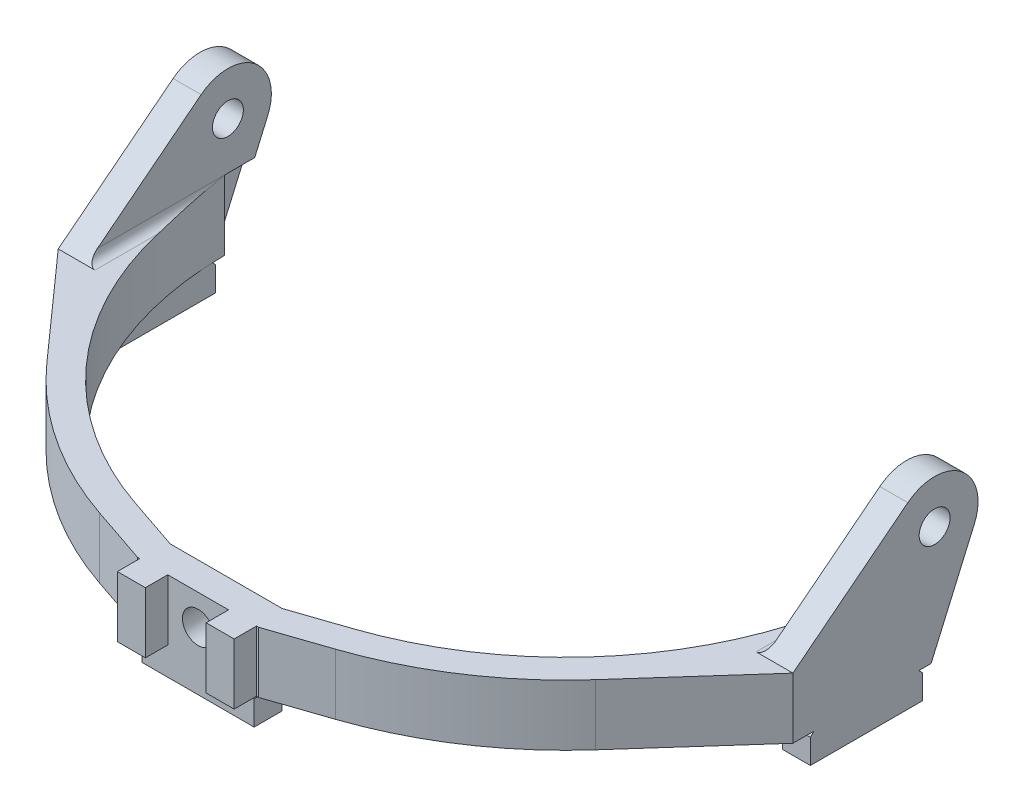
SolidWorks part; units mm, degrees
ref_plane "Front Plane" through (0, 0, 0) normal (0, 0, 1) x (1, 0, 0)
ref_plane "Top Plane" through (0, 0, 0) normal (0, 1, 0) x (1, 0, 0)
ref_plane "Right Plane" through (0, 0, 0) normal (1, 0, 0) x (0, 0, -1)
sketch "Sketch1" plane through (0, 0, 0) normal (0, 1, 0) x (1, 0, 0)
  line L0 (-38.1, 0) -> (38.1, 0) construction
  line L1 (0, 0) -> (0, -38.1) construction
  line L2 (6.35, -38.5) -> (-6.35, -38.5)
  line L3 (-6.35, -38.5) -> (-12.3637, -36.4608)
  line L4 (6.35, -38.5) -> (12.3637, -36.4608)
  line L6 (-41.675, -15.875) -> (-41.675, -0.2)
  line L7 (41.675, -0.2) -> (38.4995, -0.2)
  line L8 (-41.675, -0.2) -> (-38.4995, -0.2)
  line L10 (-41.675, -15.875) -> (-41.675, -15.875)
  line L11 (-41.675, -15.875) -> (-41.675, -15.875)
  line L12 (-41.675, -15.875) -> (-41.675, -15.875)
  line L14 (-6.8737, -41.675) -> (-13.3833, -39.4676)
  line L15 (6.8737, -41.675) -> (-6.8737, -41.675)
  line L16 (6.8737, -41.675) -> (13.3833, -39.4676)
  line L18 (-41.675, 0) -> (-41.675, -12.7) construction
  line L21 (41.675, -15.875) -> (41.675, -0.2)
  line L23 (-41.675, -15.875) -> (-31.1132, -27.7268)
  line L25 (41.675, -15.875) -> (31.1132, -27.7268)
  line L28 (-38.533, -15.875) -> (-41.675, -15.875) construction
  line L29 (-36.345, -12.7) -> (-38.5, -12.7) construction
  line L30 (-38.5, 0) -> (-38.5, -12.7) construction
  line L31 (-41.675, 0) -> (-38.5, 0) construction
  arc A0 (-38.1, 0) -> (38.1, 0) centre (0, 0) ccw construction
  arc A1 (-36.345, -12.7) -> (-12.3637, -36.4608) centre (0, 0) ccw
  arc A2 (38.4995, -0.2) -> (36.345, -12.7) centre (0, 0) cw
  arc A3 (-38.4995, -0.2) -> (-36.345, -12.7) centre (0, 0) ccw
  arc A4 (-38.5, 0) -> (38.5, 0) centre (0, 0) ccw construction
  arc A5 (13.3833, -39.4676) -> (31.1132, -27.7268) centre (0, 0) ccw
  arc A6 (-31.1132, -27.7268) -> (-13.3833, -39.4676) centre (0, 0) ccw
  arc A7 (13.3833, -39.4676) -> (41.675, 0) centre (0, 0) ccw construction
  arc A8 (12.3637, -36.4608) -> (38.5, 0) centre (0, 0) ccw construction
  arc A9 (36.345, -12.7) -> (12.3637, -36.4608) centre (0, 0) cw
  arc A10 (-38.533, -15.875) -> (-13.3833, -39.4676) centre (0, 0) ccw construction
  point P11 (0, -38.5)
  point P32 (-40.4898, -14.8188)
  point P34 (-27.8424, -31.3971)
  point P35 (-26.6572, -30.3409)
  dimension "D1" = 0.4
  dimension "D2" = 6.35
  dimension "D3" = 0.2
  dimension "D5" = 3.175
extrude "Boss-Extrude2" add sketch "Sketch1" along normal blind 6.896 contours L23 A6 L14 L15 L16 A5 L25 L21 L4 L2 L3 A1 L6 region at (9.6558, 0, 38.3621)
ref_plane "Plane1" through (41.675, 0, 0) normal (1, 0, 0) x (0, 0, -1)
sketch "Sketch2" plane through (41.675, 0, 0) normal (1, 0, 0) x (0, 0, -1)
  line L0 (0.2, 6.896) -> (0.2, 13.246) construction
  line L2 (-15.875, 6.896) -> (-2.8419, 17.1226)
  line L3 (-0.2, 6.896) -> (-15.875, 6.896)
  line L4 (-0.2, 0) -> (-0.2, 6.896)
  line L5 (-0.2, 0) -> (4.7169, 11.2765)
  circle A0 centre (0.2, 13.246) radius 1.7526
  arc A1 (4.7169, 11.2765) -> (-2.8419, 17.1226) centre (0.2, 13.246) ccw
  circle A3 centre (0.2, 13.246) radius 4.9276 construction
  point P3 (-0.2, 13.246)
  point P5 (0, 13.246)
  point P6 (0, 13.246)
  point P7 (0, 13.246)
  point P10 (6.9802, 13.246)
  point P12 (4.7276, 13.246)
  point P14 (5.1276, 13.246)
  point P15 (5.2276, 13.246)
  point P17 (5.0276, 13.246)
  dimension "D3" = 3.175
  dimension "D4" = 3.5052
  dimension "D2" = 0.4
  dimension "D1" = 6.35
extrude "Boss-Extrude3" add sketch "Sketch2" against normal blind 3.175
sketch "Sketch3" plane through (0, 6.896, 0) normal (0, 1, 0) x (1, 0, 0)
  line L0 (0, -41.675) -> (0, 0) construction
  line L1 (6.8737, -41.675) -> (-6.8737, -41.675) construction
ref_plane "Plane2" through (0, 0, 0) normal (-1, 0, 0) x (0, 0, 1)
mirror "Mirror1" about plane through (0, 0, 0) normal (-1, 0, 0) of "Boss-Extrude3"
chamfer "Chamfer4" [suppressed] distance 1 angle 45
sketch "Sketch6" [suppressed] plane through (0, 0, 41.675) normal (0, 0, 1) x (1, 0, 0)
  line L0 (0, 0) -> (0, 6.896) construction
  line L1 (-6.7087, 6.896) -> (6.7087, 6.896) construction
  line L4 (3.448, 0) -> (3.448, 6.896)
  line L6 (-3.448, 0) -> (-3.448, 6.896)
  line L7 (3.448, 0) -> (-3.448, 6.896) construction
  line L8 (3.448, 6.896) -> (-3.448, 0) construction
  line L9 (-3.448, 6.896) -> (-6.623, 6.896)
  line L10 (-3.448, 6.896) -> (-3.448, 0)
  line L11 (-3.448, 0) -> (-6.623, 0)
  line L12 (-6.623, 6.896) -> (-6.623, 0)
  line L15 (3.448, 6.896) -> (6.623, 6.896)
  line L16 (3.448, 6.896) -> (3.448, 0)
  line L17 (3.448, 0) -> (6.623, 0)
  line L18 (6.623, 6.896) -> (6.623, 0)
  point P5 (0, 3.448)
  dimension "D1" = 6.896
  dimension "D2" = 6.896
  dimension "D3" = 3.175
  dimension "D4" = 3.175
hole_wizard "9/64 (0.14063) Diameter Hole2" positions "Sketch8" profile "Sketch7" hole size "9/64" standard "ANSI Inch" end condition through all
sketch "Sketch8" plane through (0, 0, 41.675) normal (0, 0, 1) x (1, 0, 0)
  line L0 (0, 0) -> (0, 6.896) construction
  line L1 (6.8737, 6.896) -> (-6.8737, 6.896) construction
  point P12 (0, 3.448)
  dimension "D1" = 3.448
sketch "Sketch7" plane through (0, 3.448, 41.675) normal (1, 0, 0) x (0, -1, 0)
  line L0 (0, 0) -> (0, 46.8026)
  line L1 (0, 46.8026) -> (1.786, 46.8026)
  line L2 (1.786, 46.8026) -> (1.786, 0)
  line L5 (1.786, 0) -> (0, 0)
  line L11 (0, -6.35) -> (0, 107.95) construction
  dimension "Thru Hole Dia." = 3.572
  dimension "Thru Hole Depth" = 46.8026
sketch "Sketch9" plane through (0, 0, 41.675) normal (0, 0, 1) x (1, 0, 0)
  line L0 (0, 6.896) -> (0, 0) construction
  line L1 (6.8737, 6.896) -> (-6.8737, 6.896) construction
  line L2 (6.8737, 0) -> (-6.8737, 0) construction
  line L3 (-6.623, 6.896) -> (-3.448, 6.896)
  line L4 (-6.623, 6.896) -> (-6.623, 0)
  line L5 (-6.623, 0) -> (-3.448, 0)
  line L6 (-3.448, 6.896) -> (-3.448, 0)
  line L7 (6.623, 0) -> (3.448, 0)
  line L8 (6.623, 6.896) -> (3.448, 6.896)
  line L9 (6.623, 6.896) -> (6.623, 0)
  line L10 (3.448, 6.896) -> (3.448, 0)
  dimension "D1" = 3.175
  dimension "D2" = 3.448
extrude "Boss-Extrude5" add sketch "Sketch9" along normal blind 2.54
sketch "Sketch10" plane through (0, 0, 0) normal (0, -1, 0) x (-1, 0, 0)
  line L0 (-6.35, -38.5) -> (6.35, -38.5) construction
  line L1 (41.675, -13.8955) -> (38.5, -13.8955)
  line L2 (-41.675, -13.8955) -> (-38.5, -13.8955)
  line L3 (41.675, -13.8955) -> (41.675, -1.1955)
  line L4 (-41.675, -13.8955) -> (-41.675, -1.1955)
  line L5 (-41.675, -1.1955) -> (-38.5, -1.1955)
  line L6 (-38.5, -13.8955) -> (-38.5, -1.1955)
  line L7 (41.675, -1.1955) -> (38.5, -1.1955)
  line L8 (0, -5.5391) -> (0, 5.5391) construction
  line L9 (41.675, -7.5455) -> (-41.675, -7.5455) construction
  line L10 (41.675, -15.875) -> (41.675, -0.2) construction
  line L11 (-41.675, 3.7928) -> (-41.675, -3.7928) construction
  line L12 (38.5, -13.8955) -> (38.5, -1.1955)
  line L13 (-6.35, -38.5) -> (6.35, -38.5)
  line L14 (-6.35, -38.5) -> (-6.35, -41.675)
  line L15 (-6.35, -41.675) -> (6.35, -41.675)
  line L16 (6.35, -38.5) -> (6.35, -41.675)
  line L18 (0, -41.675) -> (0, 0) construction
  point P9 (0, -41.675)
  point P19 (-38.5, -7.5455)
  point P24 (0, -41.675)
  point P25 (38.5, -7.5455)
  dimension "D1" = 3.175
  dimension "D2" = 3.175
  dimension "D3" = 12.7
  dimension "D4" = 12.7
extrude "Boss-Extrude6" add sketch "Sketch10" along normal blind 3.175
sketch "Sketch11" plane through (-41.675, 0, 0) normal (-1, 0, 0) x (0, 0, 1)
  line L0 (13.8955, -0.4) -> (13.4955, 0)
  line L1 (13.8955, -3.175) -> (13.8955, 0) construction
  line L2 (13.4955, 0) -> (13.8955, 0)
  line L3 (13.8955, 0) -> (13.8955, -0.4)
  line L4 (7.5455, -3.175) -> (7.5455, 0) construction
  line L5 (13.8955, -3.175) -> (1.1955, -3.175) construction
  line L6 (1.5955, 0) -> (1.1955, 0)
  line L7 (1.1955, 0) -> (1.1955, -0.4)
  line L8 (1.1955, -0.4) -> (1.5955, 0)
  dimension "D1" = 0.4
  dimension "D2" = 0.4
extrude "Cut-Extrude1" cut sketch "Sketch11" against normal through all
sketch "Sketch12" plane through (0, 0, 41.675) normal (0, 0, 1) x (1, 0, 0)
  line L0 (6.35, -0.4) -> (6.35, 0)
  line L1 (6.35, -3.175) -> (6.35, 0) construction
  line L2 (6.35, 0) -> (5.95, 0)
  line L3 (6.35, 0) -> (3.448, 0) construction
  line L4 (5.95, 0) -> (6.35, -0.4)
  line L5 (0, -3.175) -> (0, 0) construction
  line L6 (6.35, -3.175) -> (-6.35, -3.175) construction
  line L7 (-5.95, 0) -> (-6.35, -0.4)
  line L8 (-6.35, -0.4) -> (-6.35, 0)
  line L9 (-6.35, 0) -> (-5.95, 0)
  dimension "D1" = 0.4
  dimension "D2" = 0.4
extrude "Cut-Extrude2" cut sketch "Sketch12" against normal through all
fillet "Fillet2" radius 1 2 edges at (-38.5, 6.896, 8.0375) (38.5, 6.896, 8.0375)
sketch "Sketch14" plane through (-38.5, 0, 0) normal (1, 0, 0) x (0, 0, -1)
  line L0 (-0.2, 0) -> (-0.2, 7.896)
  line L1 (-0.2, 7.896) -> (3.2429, 7.896)
  line L2 (-0.2, 0) -> (4.7169, 11.2765) construction
  line L3 (3.2429, 7.896) -> (-0.2, 0)
extrude "Cut-Extrude3" cut sketch "Sketch14" against normal blind 1
mirror "Mirror2" about plane through (0, 0, 0) normal (-1, 0, 0) of "Cut-Extrude3"
